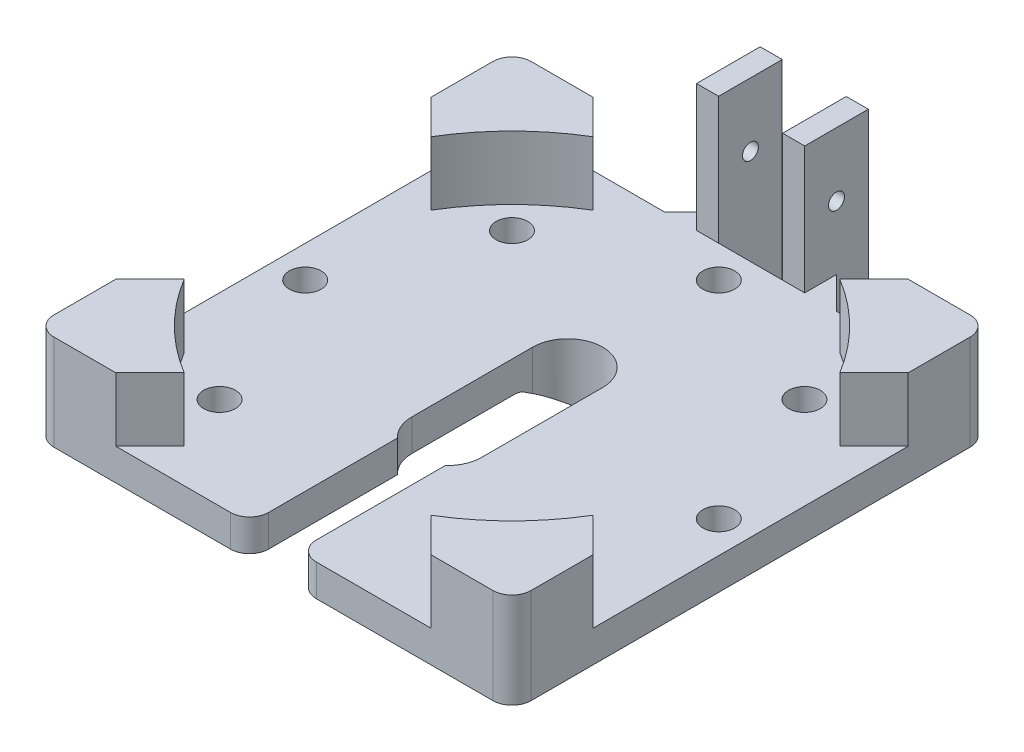
SolidWorks part; units mm, degrees
ref_plane "Front Plane" through (0, 0, 0) normal (0, 0, 1) x (1, 0, 0)
ref_plane "Top Plane" through (0, 0, 0) normal (0, 1, 0) x (1, 0, 0)
ref_plane "Right Plane" through (0, 0, 0) normal (1, 0, 0) x (0, 0, -1)
sketch "Sketch1" plane through (0, 0, 0) normal (0, 1, 0) x (1, 0, 0)
  line L1 (-95.25, -95.25) -> (95.25, -95.25)
  line L2 (-95.25, -95.25) -> (-95.25, 95.25)
  line L3 (-95.25, 95.25) -> (95.25, 95.25)
  line L4 (95.25, -95.25) -> (95.25, 95.25)
  line L5 (-95.25, -95.25) -> (95.25, 95.25) construction
  line L6 (-95.25, 95.25) -> (95.25, -95.25) construction
  point P0 (0, 0)
  dimension "D1" = 190.5
  dimension "D2" = 190.5
extrude "Boss-Extrude1" add sketch "Sketch1" along normal blind 12.7
fillet "Fillet1" radius 7.62 4 edges at (-95.25, 6.35, 95.25) (95.25, 6.35, 95.25) (95.25, 6.35, -95.25) (-95.25, 6.35, -95.25)
ref_plane "Plane1" through (12.7, 0, 0) normal (1, 0, 0) x (0, 0, -1)
sketch "Sketch2" plane through (12.7, 0, 0) normal (1, 0, 0) x (0, 0, -1)
  line L0 (95.25, 12.7) -> (95.25, 63.5)
  line L1 (95.25, 63.5) -> (120.65, 63.5)
  line L2 (120.65, 63.5) -> (120.65, -50.8)
  line L3 (120.65, -50.8) -> (95.25, -50.8)
  line L4 (95.25, -50.8) -> (17.0249, 0)
  line L5 (-87.63, 0) -> (87.63, 0) construction
  line L6 (17.0249, 0) -> (95.25, 0)
  line L7 (95.25, 0) -> (95.25, -50.8)
  line L8 (95.25, 12.7) -> (95.25, 0)
  line L9 (95.25, 12.7) -> (95.25, 0) construction
  dimension "D1" = 50.8
  dimension "D2" = 25.4
  dimension "D3" = 114.3
  dimension "D4" = 147
  dimension "D5" = 25.4
  dimension "D6" = 63.5
extrude "Boss-Extrude2" add sketch "Sketch2" along normal blind 8.89 and the other way blind 34.29 contours L7 L6 L4 | L0 L8 L7 L3 L2 L1 region at (12.7, 6.35, -107.95) region at (12.7, -16.9333, -69.175)
extrude "Cut-Extrude1" cut sketch "Sketch2<3>" against normal blind 25.4762 and the other way blind 0.0762 contours L0 L8 L7 L3 L2 L1 region at (12.7, 6.35, -107.95)
sketch "Sketch2<3>" plane through (12.7, 0, 0) normal (1, 0, 0) x (0, 0, -1) same geometry as "Sketch2"
hole_wizard "1/4 (0.25) Diameter Hole1" positions "Sketch3" profile "Sketch5" hole size "1/4" standard "ANSI Inch" end condition through all
sketch "Sketch3" plane through (21.59, 0, 0) normal (1, 0, 0) x (0, 0, -1)
  line L0 (95.25, 12.7) -> (95.25, 63.5) construction
  line L1 (-87.63, 12.7) -> (87.63, 12.7) construction
  point P0 (107.95, 38.1)
  dimension "D1" = 12.7
  dimension "D2" = 25.4
sketch "Sketch5" plane through (21.59, 38.1, -107.95) normal (0, 1, 0) x (0, 0, -1)
  line L0 (0, 0) -> (0, 116.84)
  line L1 (0, 116.84) -> (3.175, 116.84)
  line L2 (3.175, 116.84) -> (3.175, 0)
  line L5 (3.175, 0) -> (0, 0)
  line L11 (0, -6.35) -> (0, 107.95) construction
  dimension "Thru Hole Dia." = 6.35
  dimension "Thru Hole Depth" = 116.84
fillet "Fillet2" radius 7.62 1 edges at (0, 0, -17.0249)
sketch "Sketch6" plane through (0, 12.7, 0) normal (0, 1, 0) x (1, 0, 0)
  line L0 (-95.25, 87.63) -> (-95.25, -87.63) construction
  line L1 (-82.55, -82.55) -> (82.55, -82.55)
  line L2 (-82.55, -82.55) -> (-82.55, 82.55)
  line L3 (-82.55, 82.55) -> (82.55, 82.55)
  line L4 (82.55, -82.55) -> (82.55, 82.55)
  line L5 (-82.55, -82.55) -> (82.55, 82.55) construction
  line L6 (-82.55, 82.55) -> (82.55, -82.55) construction
  line L7 (-87.63, -95.25) -> (87.63, -95.25) construction
  point P0 (0, 0)
  dimension "D1" = 12.7
  dimension "D2" = 12.7
chamfer "Chamfer1" distance 16.51 angle 45 2 edges at (21.59, 0, -55.0089) (-21.59, 0, -55.0089)
sketch "Sketch7" plane through (0, 12.7, 0) normal (0, 1, 0) x (1, 0, 0)
  line L0 (95.25, 95.25) -> (-95.25, -95.25) construction
  line L1 (62.9211, 95.25) -> (49.2652, 81.5941)
  line L2 (81.5941, 49.2652) -> (95.25, 62.9211)
  line L8 (95.25, -87.63) -> (95.25, 87.63)
  line L9 (87.63, 95.25) -> (21.59, 95.25)
  line L10 (21.59, 95.25) -> (12.7762, 95.25)
  line L11 (12.7762, 95.25) -> (-12.7762, 95.25)
  line L12 (-12.7762, 95.25) -> (-21.59, 95.25)
  line L13 (-21.59, 95.25) -> (-87.63, 95.25)
  line L14 (-95.25, 87.63) -> (-95.25, -87.63)
  line L15 (-87.63, -95.25) -> (87.63, -95.25)
  line L16 (95.25, -87.63) -> (95.25, 87.63)
  line L17 (87.63, 95.25) -> (21.59, 95.25)
  line L18 (21.59, 95.25) -> (12.7762, 95.25)
  line L19 (12.7762, 95.25) -> (-12.7762, 95.25)
  line L20 (-12.7762, 95.25) -> (-21.59, 95.25)
  line L21 (-21.59, 95.25) -> (-87.63, 95.25)
  line L22 (-95.25, 87.63) -> (-95.25, -87.63)
  line L23 (-87.63, -95.25) -> (87.63, -95.25)
  circle A0 centre (0, 0) radius 95.3135
  arc A5 (95.25, 87.63) -> (87.63, 95.25) centre (87.63, 87.63) ccw
  arc A6 (-87.63, 95.25) -> (-95.25, 87.63) centre (-87.63, 87.63) ccw
  arc A7 (-95.25, -87.63) -> (-87.63, -95.25) centre (-87.63, -87.63) ccw
  arc A8 (87.63, -95.25) -> (95.25, -87.63) centre (87.63, -87.63) ccw
  arc A9 (95.25, 87.63) -> (87.63, 95.25) centre (87.63, 87.63) ccw
  arc A10 (-87.63, 95.25) -> (-95.25, 87.63) centre (-87.63, 87.63) ccw
  arc A11 (-95.25, -87.63) -> (-87.63, -95.25) centre (-87.63, -87.63) ccw
  arc A12 (87.63, -95.25) -> (95.25, -87.63) centre (87.63, -87.63) ccw
  line M17 (95.25, -87.63) -> (95.25, 87.63)
  arc M18 (95.25, 87.63) -> (87.63, 95.25) centre (87.63, 87.63) ccw
  line M19 (87.63, 95.25) -> (21.59, 95.25)
  dimension "D3" = 190.627
  dimension "D2" = 190.5
  dimension "D4" = 45
  dimension "D5" = 7.62
  dimension "D6" = 7.62
  dimension "D7" = 22.86
  dimension "D8" = 22.86
  dimension "D1" = 0
extrude "Boss-Extrude3" add sketch "Sketch7" along normal blind 25.4 contours L0 A9 L1 A0 M19 | L0 A0 L2 M18 M17 region at (84.5318, 12.7, -70.1242) region at (70.1242, 12.7, -84.5318)
ref_axis "Axis1" through (0, 195.7992, 0) along (0, -1, 0)
pattern_circular "CirPattern1" count 4 over 360 about axis through (0, 195.7992, 0) along (0, -1, 0) of "Boss-Extrude3"
sketch "Sketch8" plane through (0, 12.7, 0) normal (0, 1, 0) x (1, 0, 0)
  circle A0 centre (0, 0) radius 82.55
  circle A1 centre (0, 82.55) radius 6.35
  circle A2 centre (58.3717, 58.3717) radius 6.35
  circle A3 centre (82.55, 0) radius 6.35
  circle A4 centre (58.3717, -58.3717) radius 6.35
  circle A5 centre (0, -82.55) radius 6.35
  circle A6 centre (-58.3717, -58.3717) radius 6.35
  circle A7 centre (-82.55, 0) radius 6.35
  circle A8 centre (-58.3717, 58.3717) radius 6.35
  point P21 (0, 0)
  dimension "D1" = 165.1
  dimension "D2" = 12.7
  dimension "D3" = 8
extrude "Cut-Extrude2" cut sketch "Sketch8" against normal blind 25.4 contours A1 | A8 | A7 | A6 | A5 | A4 | A3 | A2
sketch "Sketch10" plane through (0, 12.7, 0) normal (0, 1, 0) x (1, 0, 0)
  line L0 (-13.97, 22.225) -> (-13.97, -36.195)
  line L2 (13.97, 22.225) -> (13.97, -36.195)
  line L4 (-13.97, -36.195) -> (13.97, -36.195)
  line L5 (-9.525, -36.195) -> (-9.525, -95.25)
  line L6 (-62.9211, -95.25) -> (62.9211, -95.25) construction
  line L7 (0, -95.25) -> (0, 48.459) construction
  line L8 (9.525, -36.195) -> (9.525, -95.25)
  line L9 (-9.525, -95.25) -> (9.525, -95.25)
  arc A0 (13.97, 22.225) -> (-13.97, 22.225) centre (0, 22.225) ccw
  circle M9 centre (0, -82.55) radius 6.35
  line M20 (-62.9211, -95.25) -> (62.9211, -95.25)
  dimension "D2" = 27.94
  dimension "D1" = 22.225
  dimension "D3" = 58.42
  dimension "D4" = 9.525
  dimension "D5" = 19.05
extrude "Cut-Extrude3" cut sketch "Sketch10" against normal through all contours L7 L9 L8 L4 M9 | L7 L4 L5 M20 M9 | A0 L0 L4 L2 region at (-5.0248, 12.7, 63.5873) region at (5.0248, 12.7, 63.5873)
fillet "Fillet3" radius 7.62 2 edges at (9.525, 6.35, 95.25) (-9.525, 6.35, 95.25)
fillet "Fillet4" radius 13.97 2 edges at (13.97, 6.35, 36.195) (-13.97, 6.35, 36.195)
chamfer "Chamfer2" distance 12.7 angle 45 2 edges at (-21.59, -1.905, -95.25) (21.59, -1.905, -95.25)
sketch "Sketch11" plane through (-21.59, 0, 0) normal (-1, 0, 0) x (0, 0, 1)
  line L0 (-42.448, -16.51) -> (-107.95, -16.51) construction
  line L1 (-120.65, -50.8) -> (-60.4211, -50.8)
  line L2 (-120.65, -50.8) -> (-120.65, -41.91)
  line L3 (-120.65, -41.91) -> (-60.4211, -41.91)
  line L4 (-60.4211, -50.8) -> (-60.4211, -41.91)
  dimension "D1" = 25.4
extrude "Cut-Extrude4" cut sketch "Sketch11" against normal through all
